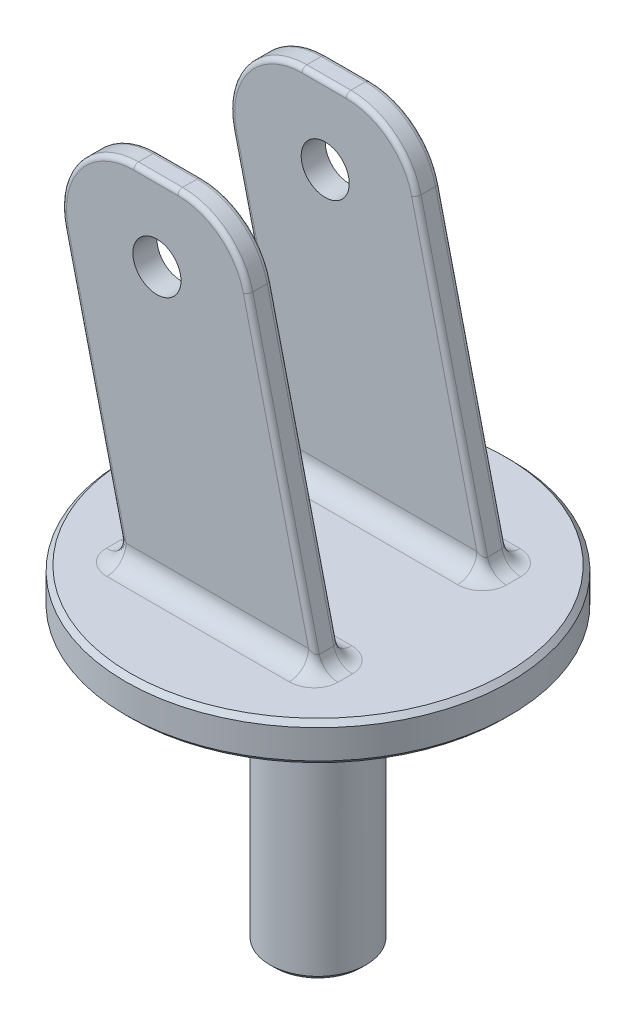
SolidWorks part; units mm, degrees
ref_plane "Front Plane" through (0, 0, 0) normal (0, 0, 1) x (1, 0, 0)
ref_plane "Top Plane" through (0, 0, 0) normal (0, 1, 0) x (1, 0, 0)
ref_plane "Right Plane" through (0, 0, 0) normal (1, 0, 0) x (0, 0, -1)
sketch "Sketch2" plane through (0, 0, 0) normal (0, 1, 0) x (1, 0, 0)
  circle A0 centre (0, 0) radius 40
  dimension "D1" = 80
extrude "Boss-Extrude1" add sketch "Sketch2" along normal blind 8
sketch "Sketch6" plane through (0, 0, 0) normal (0, -1, 0) x (1, 0, 0)
  circle A0 centre (0, 0) radius 10
  circle A1 centre (0, 0) radius 7.5
  dimension "D1" = 20
  dimension "D2" = 15
extrude "Boss-Extrude4" add sketch "Sketch6" along normal blind 60
chamfer "Chamfer1" distance 1 angle 45 3 edges at (0, 0, 40) (0, 8, 40) (0, -60, -10)
sketch "Sketch20" plane through (0, 0, 0) normal (0, 0, 1) x (1, 0, 0)
  line L0 (0, 0) -> (-34.9854, 147.6672) construction
sketch "Sketch19" plane through (0, 8, 0) normal (0, 1, 0) x (1, 0, 0)
  line L0 (0, 0) -> (0, 39) construction
  line L2 (20, 20) -> (-20, 20)
  line L3 (20, 20) -> (20, 15)
  line L4 (20, 15) -> (-20, 15)
  line L5 (-20, 20) -> (-20, 15)
  line L6 (20, 20) -> (-20, 15) construction
  line L7 (20, 15) -> (-20, 20) construction
  circle A0 centre (0, 0) radius 39 construction
  point P6 (0, 17.5)
  dimension "D1" = 40
  dimension "D2" = 15
  dimension "D3" = 5
extrude "Boss-Extrude5" add sketch "Sketch19" along direction (-0.2305, 0.9731, 0) on the side of the normal blind 75
fillet "Fillet1" radius 15 2 edges at (2.7096, 80.9797, -17.5) (-37.2904, 80.9797, -17.5)
fillet "Fillet2" radius 1 10 edges at (12.7221, 38.7189, -20) (0.1522, 77.7456, -20) (-13.7366, 80.9797, -20) (-30.0872, 75.2837, -20) (12.7221, 38.7189, -15) (0.1522, 77.7456, -15) (-13.7366, 80.9797, -15) (-30.0872, 75.2837, -15) (-26.4587, 35.2608, -20) (-26.4587, 35.2608, -15)
fillet "Fillet3" radius 4 8 edges at (-19.699, 8, -15.2929) (-20, 8, -17.5) (-19.699, 8, -19.7071) (0, 8, -20) (19.699, 8, -19.7071) (20, 8, -17.5) (19.699, 8, -15.2929) (0, 8, -15)
mirror "Mirror2" about plane through (0, 0, 0) normal (0, 0, 1) of "Boss-Extrude5", "Fillet1", "Fillet2", "Fillet3"
sketch "Sketch21" plane through (0, 0, 20) normal (0, 0, 1) x (1, 0, 0)
  line L0 (-9.1518, 79.9797) -> (-18.3214, 79.9797) construction
  line L1 (-31.9442, 62.7522) -> (-19.92, 12) construction
  line L2 (18.0246, 12) -> (4.4711, 69.2073) construction
  circle A0 centre (-13.501, 64.9797) radius 5
  dimension "D1" = 10
  dimension "D2" = 15
  dimension "D3" = 18.46
  dimension "D4" = 18.4625
extrude "Cut-Extrude1" cut sketch "Sketch21" against normal up to surface (40 mm away) up to face at (-9.8566, 53.5974, -20)
